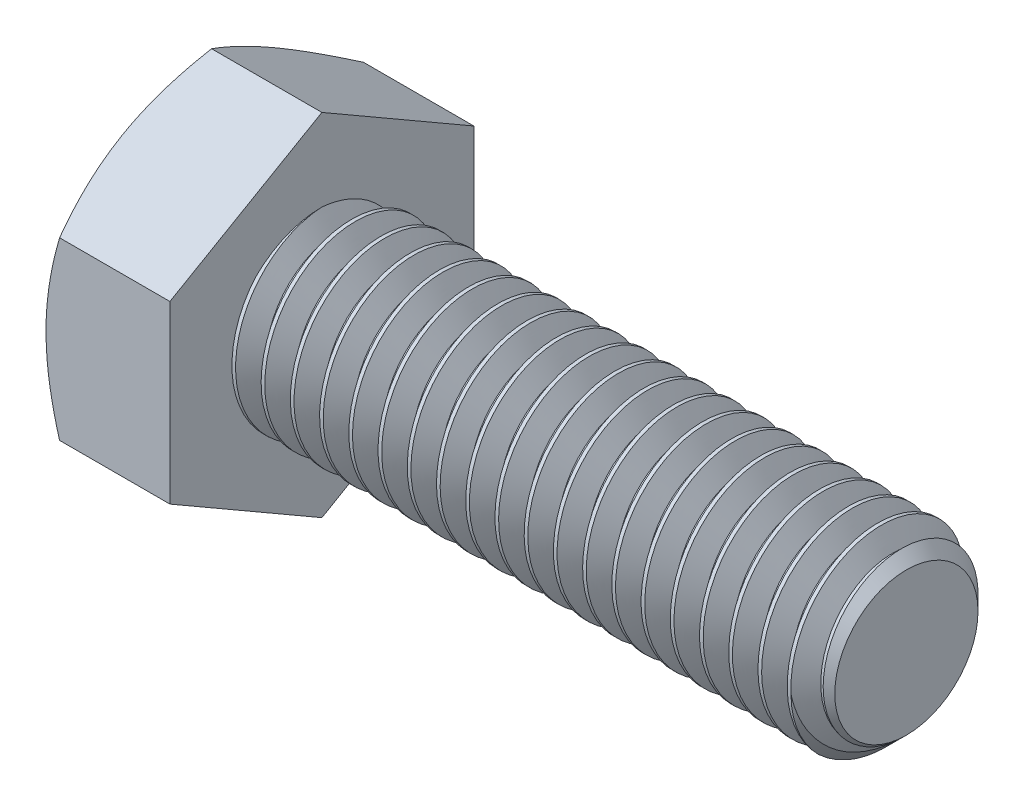
SolidWorks part; units mm, degrees
material "Plain Carbon Steel"
ref_plane "Front Plane" through (0, 0, 0) normal (0, 0, 1) x (1, 0, 0)
ref_plane "Top Plane" through (0, 0, 0) normal (0, 1, 0) x (1, 0, 0)
ref_plane "Right Plane" through (0, 0, 0) normal (1, 0, 0) x (0, 0, -1)
sketch "Sketch1" plane through (0, 0, 0) normal (0, 0, 1) x (1, 0, 0)
  line L0 (-15.15, 0) -> (15.15, 0) construction
  line L1 (-9.85, 6.5) -> (-9.85, -6.5) construction
  line L2 (-15.15, 6.5) -> (-15.15, -6.5) construction
  line L3 (15.15, 4) -> (15.15, -4) construction
  point P8 (10.775, -4)
  dimension "Thread Dia" = 8
  dimension "Hex" = 13
  dimension "Head Ht" = 5.3
  dimension "Length" = 25
  dimension "D1" = 4.375
ref_plane "Plane2" through (15.15, 0, 0) normal (1, 0, 0) x (0, 0, -1)
sketch "Sketch2" plane through (15.15, 0, 0) normal (1, 0, 0) x (0, 0, -1)
  circle A0 centre (0, 0) radius 4
extrude "Boss-Extrude1" add sketch "Sketch2" against normal up to vertex (25 mm away) up to point (-9.85, -6.5, 0)
sketch "Sketch4" plane through (15.15, 0, 0) normal (1, 0, 0) x (0, 0, -1)
  circle A1 centre (0, 0) radius 4
  circle A2 centre (0, 0) radius 4
  dimension "D1" = 0
curve "Helix/Spiral1" pitch 1.25 height 26.25 turns 21 parameters "Pitch"=1.25
chamfer "Chamfer1" distance 0.9375 angle 45 1 edges at (15.15, 0, -4)
sketch "Sketch5" plane through (0, 0, 0) normal (0, 0, 1) x (1, 0, 0)
  line L0 (15.15, 4) -> (15.6187, 3.1881)
  line L1 (15.6187, 3.1881) -> (15.775, 3.1881)
  line L2 (15.775, 3.1881) -> (16.2437, 4)
  line L3 (15.15, 4) -> (16.2437, 4)
  line L4 (15.6969, 3.1881) -> (15.6969, 4) construction
  line L5 (15.3844, 3.5941) -> (16.0094, 3.5941) construction
  line L6 (15.15, -4) -> (15.15, 4) construction
  dimension "D1" = 60
  dimension "D2" = 0.1562
  dimension "D3" = 0.625
sweep "Cut-Sweep1" cut profiles "Sketch5" path "Helix/Spiral1" align with end faces yes
sketch "Sketch3" plane through (-9.85, 0, 0) normal (-1, 0, 0) x (0, 0, 1)
  line L0 (0, 6.5) -> (0, -6.5) construction
  line L1 (-6.5, -3.7528) -> (0, -7.5056)
  line L2 (0, -7.5056) -> (6.5, -3.7528)
  line L3 (6.5, -3.7528) -> (6.5, 3.7528)
  line L4 (6.5, 3.7528) -> (0, 7.5056)
  line L5 (0, 7.5056) -> (-6.5, 3.7528)
  line L6 (-6.5, 3.7528) -> (-6.5, -3.7528)
  circle A0 centre (0, 0) radius 6.5 construction
extrude "Boss-Extrude2" add sketch "Sketch3" along normal up to vertex (5.3 mm away) up to point (-15.15, -6.5, 0)
sketch "Sketch6" plane through (-15.15, 0, 0) normal (-1, 0, 0) x (0, 0, 1)
  circle A0 centre (0, 0) radius 6.5 construction
  circle A1 centre (0, 0) radius 6.5
extrude "Cut-Extrude1" cut sketch "Sketch6" against normal through all draft 60 flip side to cut
sketch "Sketch7" plane through (-15.15, 0, 0) normal (-1, 0, 0) x (0, 0, 1)
  line L0 (0, 0) -> (0, 6.5) construction
  line L2 (0, 6.5) -> (0, -6.5) construction
  line L3 (-5.6292, 3.25) -> (5.6292, 3.25) construction
  circle A1 centre (0, 0) radius 6.5 construction
  text T0 "10.9" font "Arial" height in points 8
  point P8 (0, 3.25)
extrude "Cut-Extrude2" cut sketch "Sketch7" against normal blind 0.25
sketch "Sketch9" plane through (0, 0, 0) normal (0, 0, 1) x (1, 0, 0)
  line L0 (-9.85, 4) -> (-9.85, 0)
  line L1 (-9.85, 0) -> (1.15, 0)
  line L2 (1.15, 0) -> (-2.85, 4)
  line L3 (-2.85, 4) -> (-9.85, 4)
  line L4 (-15.15, 0) -> (15.15, 0) construction
  line L5 (-9.85, 6.5) -> (-9.85, -6.5) construction
  line L6 (15.15, 4) -> (15.15, -4) construction
  dimension "D1" = 45
  dimension "MinThreadLg" = 18
revolve "Revolve1" [suppressed] add sketch "Sketch9" angle 360 about L1
equation "\"D2@Sketch5\" = \"Pitch@Helix/Spiral1\"*.125"
equation "\"D3@Sketch5\" = \"Pitch@Helix/Spiral1\"*.50"
equation "\"D3@Helix/Spiral1\" = \"Length@Sketch1\"+\"Pitch@Helix/Spiral1\""
equation "\"D1@Chamfer1\" = \"Pitch@Helix/Spiral1\"*.750"
equation "\"D1@Sketch1\" = \"Pitch@Helix/Spiral1\"*3.50"
